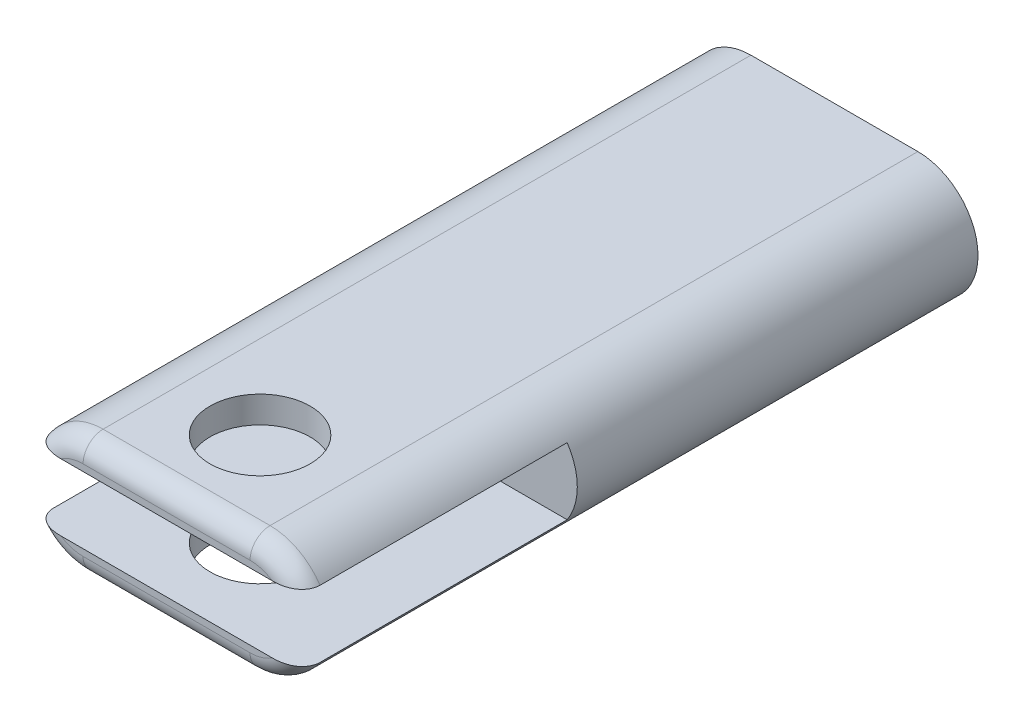
SolidWorks part; units mm, degrees
material "Wrought Stainless Steel"
ref_plane "Front Plane" through (0, 0, 0) normal (0, 0, 1) x (1, 0, 0)
ref_plane "Top Plane" through (0, 0, 0) normal (0, 1, 0) x (1, 0, 0)
ref_plane "Right Plane" through (0, 0, 0) normal (1, 0, 0) x (0, 0, -1)
sketch "Sketch1" plane through (0, 0, 0) normal (0, 0, 1) x (1, 0, 0)
  line L0 (-125, 0) -> (125, 0) construction
  line L1 (-125, 90) -> (125, 90)
  line L2 (-125, -90) -> (125, -90)
  arc A0 (-125, 90) -> (-125, -90) centre (-125, 0) ccw
  arc A1 (125, -90) -> (125, 90) centre (125, 0) ccw
  point P3 (0, 0)
  dimension "D2" = 90
  dimension "D1" = 250
extrude "Boss-Extrude1" add sketch "Sketch1" along normal blind 1000
sketch "Sketch2" plane through (0, 0, 1000) normal (0, 0, 1) x (1, 0, 0)
  line L0 (0, -50) -> (0, 50) construction
  line L10 (215.603, 50) -> (-215.7854, 50)
  line L11 (215.603, 50) -> (215.603, -50)
  line L12 (215.603, -50) -> (-215.7854, -50)
  line L13 (-215.7854, 50) -> (-215.7854, -50)
  point P3 (0, 0)
  dimension "D1" = 100
fillet "Fillet1" radius 30 4 edges at (-215, 0, 1000) (215, 0, 1000) (0, 90, 1000) (0, -90, 1000)
extrude "Cut-Extrude1" cut sketch "Sketch2" against normal blind 400
sketch "Sketch3" plane through (0, 90, 0) normal (0, 1, 0) x (1, 0, 0)
  line L0 (125, -1000) -> (-125, -1000) construction
  circle A0 centre (0, -860) radius 75
  dimension "D1" = 150
  dimension "D2" = 140
extrude "Cut-Extrude2" cut sketch "Sketch3" against normal through all
sketch "Sketch4" plane through (0, 0, 0) normal (0, 1, 0) x (1, 0, 0)
  line L0 (125, -1000) -> (-125, -1000) construction
  point P0 (0, 0)
  point P1 (0, -1000)
ref_axis "Axis1" through (0, 0, -520.936) along (0, 0, 1)
